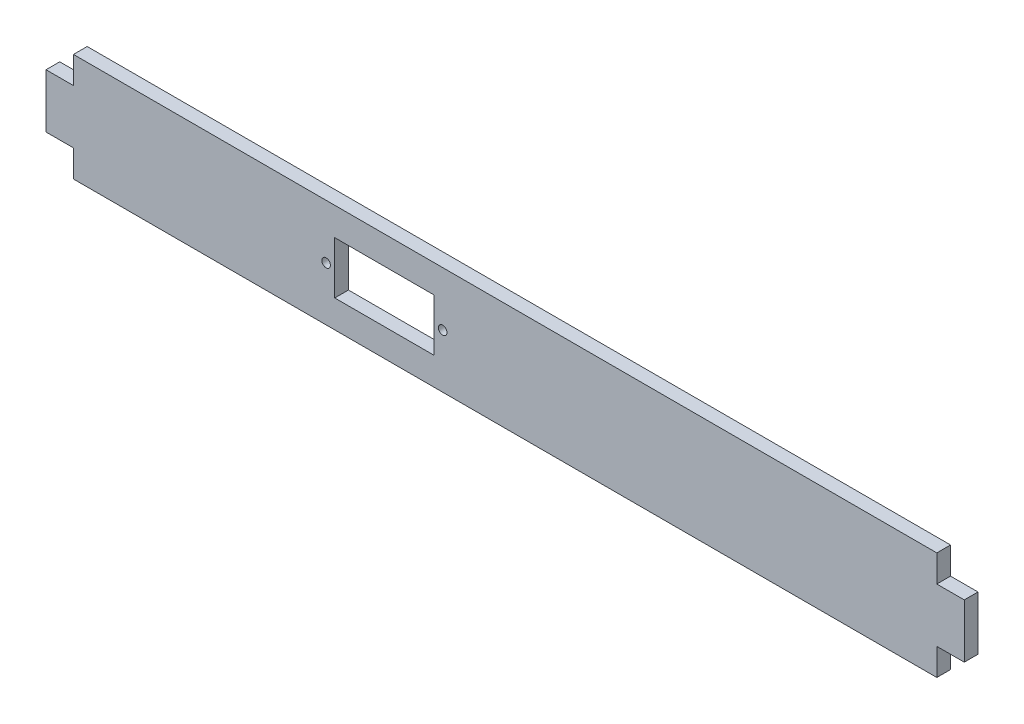
SolidWorks part; units mm, degrees
ref_plane "Front Plane" through (0, 0, 0) normal (0, 0, 1) x (1, 0, 0)
ref_plane "Top Plane" through (0, 0, 0) normal (0, 1, 0) x (1, 0, 0)
ref_plane "Right Plane" through (0, 0, 0) normal (1, 0, 0) x (0, 0, -1)
sketch "Sketch2" plane through (0, 0, 0) normal (0, 0, 1) x (1, 0, 0)
  line L1 (0, 0) -> (200, 0)
  line L2 (0, 0) -> (0, 25)
  line L3 (0, 25) -> (200, 25)
  line L4 (200, 0) -> (200, 25)
  dimension "D1" = 200
  dimension "D2" = 25
extrude "Boss-Extrude1" add sketch "Sketch2" along normal mid plane 3.18
sketch "Sketch4" plane through (0, 0, -1.59) normal (0, 0, -1) x (-1, 0, 0)
  line L0 (-72.0278, 18.5075) -> (-72.0278, 6.4075) construction
  line L1 (-83.5278, 18.5075) -> (-60.5278, 18.5075)
  line L2 (-83.5278, 18.5075) -> (-83.5278, 6.4075)
  line L3 (-83.5278, 6.4075) -> (-60.5278, 6.4075)
  line L4 (-60.5278, 18.5075) -> (-60.5278, 6.4075)
  circle A2 centre (-85.5278, 12.4575) radius 1
  circle A3 centre (-58.5278, 12.4575) radius 1
  dimension "D3" = 2
  dimension "D4" = 2
  dimension "D1" = 23
  dimension "D2" = 12.1
extrude "Cut-Extrude1" cut sketch "Sketch4" against normal blind 3.18
sketch "Sketch5" plane through (0, 0, -1.59) normal (0, 0, -1) x (-1, 0, 0)
  line L5 (-200, 0) -> (-200, 25) construction
  line L6 (-200, 18.75) -> (-206.36, 18.75)
  line L7 (-200, 18.75) -> (-200, 6.25)
  line L8 (-200, 6.25) -> (-206.36, 6.25)
  line L9 (-206.36, 18.75) -> (-206.36, 6.25)
  line L10 (0, 0) -> (-200, 0) construction
  line L11 (-100, 25) -> (-100, 0) construction
  line L12 (-200, 25) -> (0, 25) construction
  line L13 (0, 12.5) -> (-200, 12.5) construction
  line L14 (0, 25) -> (0, 0) construction
  line L15 (0, 6.25) -> (6.36, 6.25)
  line L16 (6.36, 18.75) -> (6.36, 6.25)
  line L17 (0, 18.75) -> (6.36, 18.75)
  line L18 (0, 18.75) -> (0, 6.25)
  dimension "D1" = 12.5
  dimension "D2" = 6.36
extrude "Boss-Extrude2" add sketch "Sketch5" against normal blind 3.18
equation "\"Acrylic Sheet Thickness\"= 3.18mm"
equation "\"D1@Sketch5\"=25/2"
